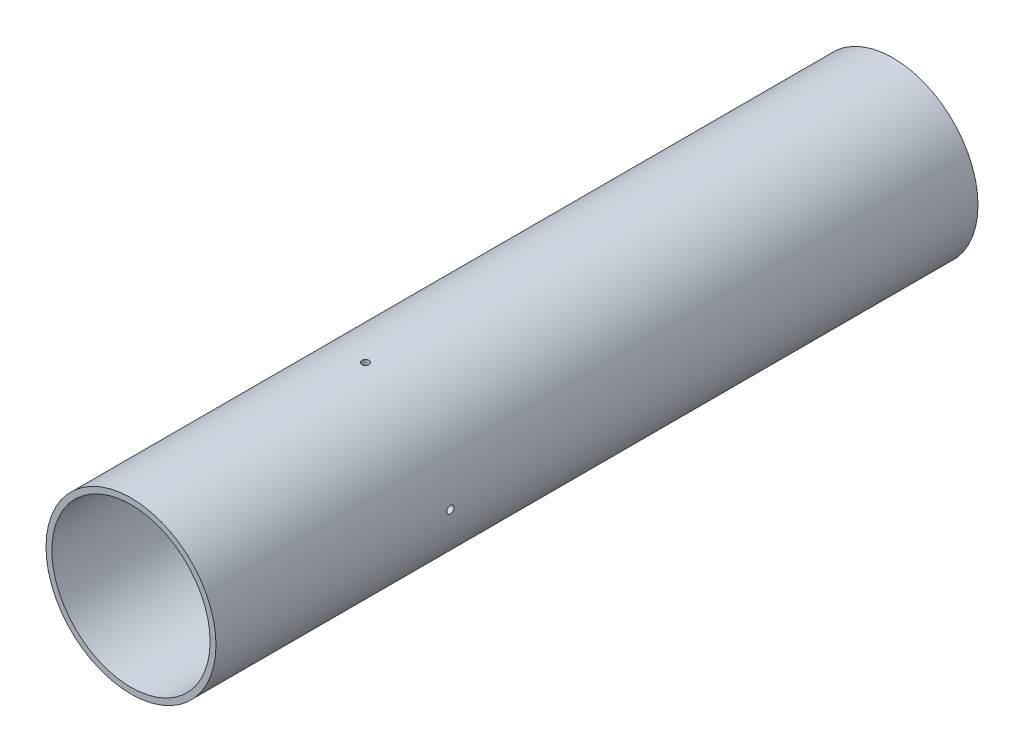
SolidWorks part; units mm, degrees
ref_plane "Front Plane" through (0, 0, 0) normal (0, 0, 1) x (1, 0, 0)
ref_plane "Top Plane" through (0, 0, 0) normal (0, 1, 0) x (1, 0, 0)
ref_plane "Right Plane" through (0, 0, 0) normal (1, 0, 0) x (0, 0, -1)
sketch "Sketch1" plane through (0, 0, 0) normal (0, 0, 1) x (1, 0, 0)
  circle A0 centre (0, 0) radius 27
  circle A1 centre (0, 0) radius 29
  dimension "D1" = 54
  dimension "D2" = 2
extrude "Boss-Extrude1" add sketch "Sketch1" along normal blind 260
ref_plane "Plane1" through (29, 0, 0) normal (1, 0, 0) x (0, 0, -1)
sketch "Sketch3" plane through (29, 0, 0) normal (1, 0, 0) x (0, 0, -1)
  line L0 (-260, 0) -> (0, 0) construction
  line L1 (-260, 29) -> (-260, -29) construction
  circle A0 centre (-180, 0) radius 1.25
  dimension "D2" = 2.5
  dimension "D1" = 80
extrude "Cut-Extrude1" cut sketch "Sketch3" against normal blind 10
ref_axis "Axis1" through (0, 0, 260) along (0, 0, -1)
pattern_circular "CirPattern1" count 4 over 360 about axis through (0, 0, 260) along (0, 0, -1) of "Cut-Extrude1"
